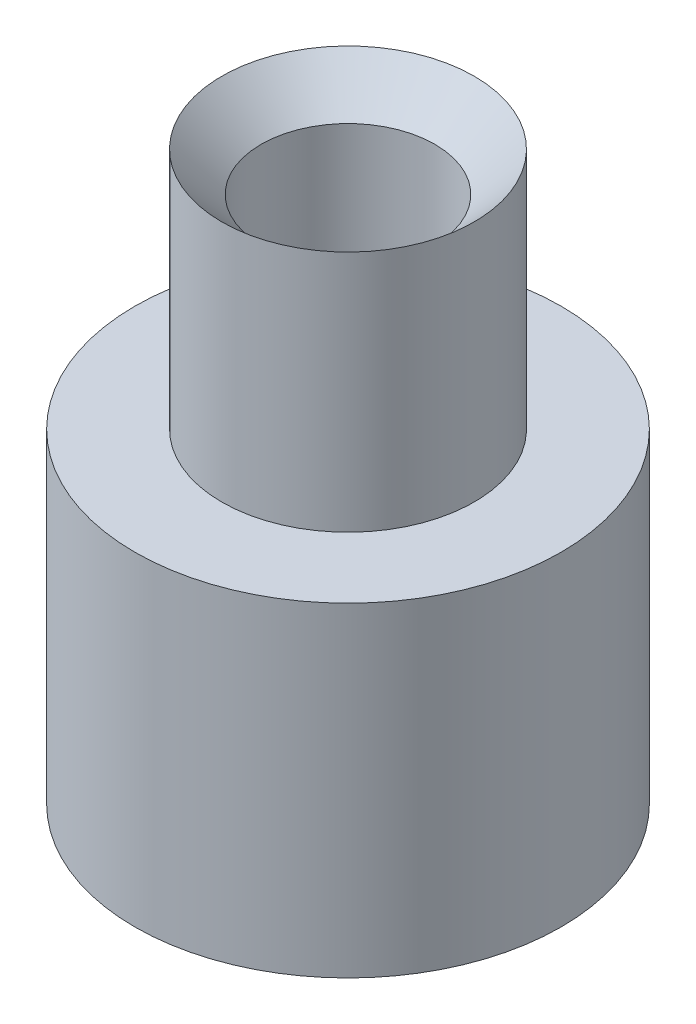
SolidWorks part; units mm, degrees
ref_plane "Plan de face" through (0, 0, 0) normal (0, 0, 1) x (1, 0, 0)
ref_plane "Plan de dessus" through (0, 0, 0) normal (0, 1, 0) x (1, 0, 0)
ref_plane "Plan de droite" through (0, 0, 0) normal (1, 0, 0) x (0, 0, -1)
sketch "Esquisse1" plane through (0, 0, 0) normal (0, 1, 0) x (1, 0, 0)
  circle A0 centre (0, 0) radius 6.5
  circle A1 centre (0, 0) radius 2.65
  dimension "D1" = 13
  dimension "D2" = 5.3
extrude "Boss.-Extru.1" add sketch "Esquisse1" along normal blind 9.9
sketch "Esquisse2" plane through (0, 9.9, 0) normal (0, 1, 0) x (1, 0, 0)
  circle A0 centre (0, 0) radius 2.65
  circle A1 centre (0, 0) radius 3.85
  dimension "D1" = 7.7
extrude "Boss.-Extru.2" add sketch "Esquisse2" along normal blind 7.5
chamfer "Chanfrein1" distance 1.3 angle 45 1 edges at (0, 17.4, 2.65)
